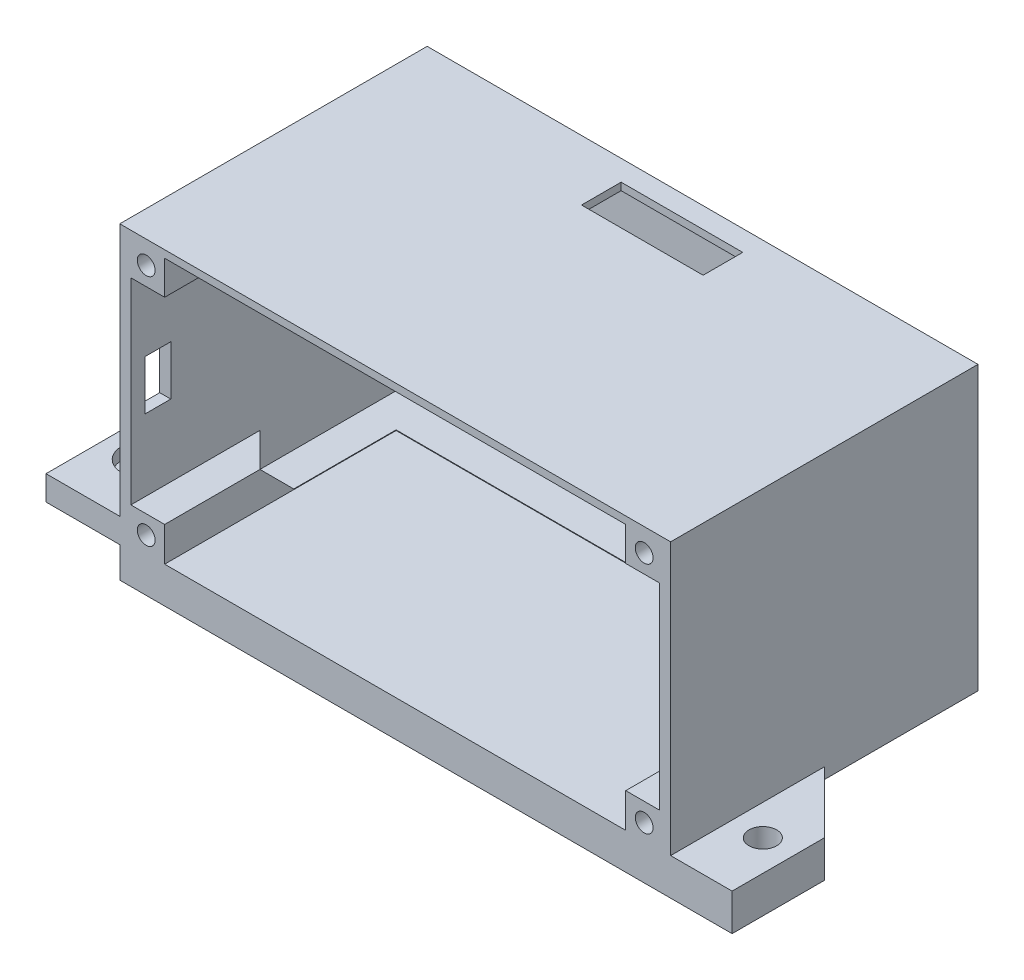
SolidWorks part; units mm, degrees
note: The reader was unsure of these and kept them because the rebuilt part matched: shared geometry of "Skizze1<3>".
ref_plane "Ebene vorne" through (0, 0, 0) normal (0, 0, 1) x (1, 0, 0)
ref_plane "Ebene oben" through (0, 0, 0) normal (0, 1, 0) x (1, 0, 0)
ref_plane "Ebene rechts" through (0, 0, 0) normal (1, 0, 0) x (0, 0, -1)
sketch "Skizze1" plane through (0, 0, 0) normal (0, 0, 1) x (1, 0, 0)
  line L0 (-44.8, 22.7) -> (-44.8, -23.3)
  line L1 (-43, -21.5) -> (43, -21.5)
  line L2 (-43, -21.5) -> (-43, 21.5)
  line L3 (-43, 21.5) -> (43, 21.5)
  line L4 (43, -21.5) -> (43, 21.5)
  line L5 (-43, -21.5) -> (43, 21.5) construction
  line L6 (-43, 21.5) -> (43, -21.5) construction
  line L7 (-44.8, -23.3) -> (44.8, -23.3)
  line L8 (44.8, -23.3) -> (44.8, 22.7)
  line L9 (44.8, 22.7) -> (-44.8, 22.7)
  point P0 (0, 0)
  dimension "D1" = 43
  dimension "D2" = 86
  dimension "D3" = 1.2
  dimension "D4" = 1.8
  dimension "D5" = 1.8
  dimension "D6" = 1.8
extrude "Aufsatz-Linear austragen1" add sketch "Skizze1" along normal blind 1 contours L1 L4 L3 L2 | L8 L9 L0 L7 L4 L1 L2 L3
extrude "Aufsatz-Linear austragen2" add sketch "Skizze1<3>" along normal blind 50
sketch "Skizze1<3>" plane through (0, 0, 0) normal (0, 0, 1) x (1, 0, 0) same geometry as "Skizze1"
sketch "Skizze2" plane through (0, 0, 50) normal (0, 0, 1) x (1, 0, 0)
  line L0 (43, 21.5) -> (-43, 21.5) construction
  line L1 (-43, -21.5) -> (-43, 21.5) construction
  line L2 (-43, 16) -> (-37.5, 16)
  line L3 (-43, 21.5) -> (-43, -21.5) construction
  line L4 (-37.5, 16) -> (-37.5, 21.5)
  line L5 (-37.5, 21.5) -> (-43, 21.5)
  line L6 (-43, 21.5) -> (-43, 16)
  line L7 (0, 0) -> (0, 11.0164) construction
  line L8 (0, 0) -> (-8.7102, 0) construction
  line L9 (-43, -21.5) -> (-43, -16)
  line L10 (-37.5, -21.5) -> (-43, -21.5)
  line L11 (-37.5, -16) -> (-37.5, -21.5)
  line L12 (-43, -16) -> (-37.5, -16)
  line L13 (43, -16) -> (37.5, -16)
  line L14 (37.5, -16) -> (37.5, -21.5)
  line L15 (37.5, -21.5) -> (43, -21.5)
  line L16 (43, -21.5) -> (43, -16)
  line L17 (43, 21.5) -> (43, 16)
  line L18 (37.5, 21.5) -> (43, 21.5)
  line L19 (37.5, 16) -> (37.5, 21.5)
  line L20 (43, 16) -> (37.5, 16)
  circle A0 centre (-40.5, 19) radius 1.45
  circle A1 centre (-40.5, -19) radius 1.45
  circle A2 centre (40.5, -19) radius 1.45
  circle A3 centre (40.5, 19) radius 1.45
  dimension "D1" = 2.9
  dimension "D2" = 2.5
  dimension "D3" = 2.5
  dimension "D4" = 3
extrude "Aufsatz-Linear austragen3" add sketch "Skizze2" against normal blind 15
sketch "Skizze3" plane through (0, 0, 35) normal (0, 0, -1) x (-1, 0, 0)
  line L0 (-43, 21.5) -> (-37.5, 21.5)
  line L1 (-37.5, 21.5) -> (-37.5, 16)
  line L2 (-37.5, 16) -> (-43, 16)
  line L3 (-43, 16) -> (-43, 21.5)
  line L4 (0, 0) -> (0, 9.0361)
  line L5 (0, 0) -> (8.9824, 0)
  line L6 (-43, -16) -> (-43, -21.5)
  line L7 (-37.5, -16) -> (-43, -16)
  line L8 (-37.5, -21.5) -> (-37.5, -16)
  line L9 (-43, -21.5) -> (-37.5, -21.5)
  line L10 (43, -21.5) -> (37.5, -21.5)
  line L11 (37.5, -21.5) -> (37.5, -16)
  line L12 (37.5, -16) -> (43, -16)
  line L13 (43, -16) -> (43, -21.5)
  line L14 (43, 16) -> (43, 21.5)
  line L15 (37.5, 16) -> (43, 16)
  line L16 (37.5, 21.5) -> (37.5, 16)
  line L17 (43, 21.5) -> (37.5, 21.5)
extrude "Aufsatz-Linear austragen4" add sketch "Skizze3" along normal blind 0.5 contours L3 L2 L1 L0 | L14 L17 L16 L15 | L13 L12 L11 L10
chamfer "Fase1" distance 5.5 angle 45 8 edges at (43, 18.75, 34.5) (40.25, 21.5, 34.5) (-40.25, -21.5, 34.5) (-43, -18.75, 34.5) (-43, 18.75, 34.5) (-40.25, 21.5, 34.5) (40.25, -21.5, 34.5) (43, -18.75, 34.5)
sketch "Skizze4" plane through (-44.8, 0, 0) normal (-1, 0, 0) x (0, 0, 1)
  line L0 (50, -0.3) -> (18.0685, -0.3) construction
  line L1 (50, 22.7) -> (50, -23.3) construction
  line L3 (43.5042, -4.3384) -> (47.6631, -4.3384)
  line L4 (43.5042, -4.3384) -> (43.5042, 3.7384)
  line L5 (43.5042, 3.7384) -> (47.6631, 3.7384)
  line L6 (47.6631, -4.3384) -> (47.6631, 3.7384)
  line L7 (43.5042, -4.3384) -> (47.6631, 3.7384) construction
  line L8 (43.5042, 3.7384) -> (47.6631, -4.3384) construction
  point P4 (45.5836, -0.3)
extrude "Schnitt-Linear austragen1" cut sketch "Skizze4" against normal blind 10
sketch "Skizze5" plane through (0, -23.3, 0) normal (0, -1, 0) x (1, 0, 0)
  line L0 (0, 0) -> (0, 29.1283) construction
  line L2 (0.8387, 3.5656) -> (22.8864, 3.5656)
  line L3 (0.8387, 3.5656) -> (0.8387, 12.3532)
  line L4 (0.8387, 12.3532) -> (22.8864, 12.3532)
  line L5 (22.8864, 3.5656) -> (22.8864, 12.3532)
  line L6 (0.8387, 3.5656) -> (22.8864, 12.3532) construction
  line L7 (0.8387, 12.3532) -> (22.8864, 3.5656) construction
  point P3 (11.8626, 7.9594)
extrude "Schnitt-Linear austragen2" cut sketch "Skizze5" against normal blind 10
sketch "Skizze6" plane through (0, 22.7, 0) normal (0, 1, 0) x (1, 0, 0)
  line L0 (0, 0) -> (0, -43.0102) construction
  line L1 (44.8, 0) -> (-44.8, 0) construction
  line L3 (-9.8897, -9.8025) -> (9.8897, -9.8025)
  line L4 (-9.8897, -9.8025) -> (-9.8897, -3.3605)
  line L5 (-9.8897, -3.3605) -> (9.8897, -3.3605)
  line L6 (9.8897, -9.8025) -> (9.8897, -3.3605)
  line L7 (-9.8897, -9.8025) -> (9.8897, -3.3605) construction
  line L8 (-9.8897, -3.3605) -> (9.8897, -9.8025) construction
  point P4 (0, -6.5815)
extrude "Schnitt-Linear austragen3" cut sketch "Skizze6" against normal blind 10
sketch "Skizze7" plane through (0, -23.3, 0) normal (0, -1, 0) x (1, 0, 0)
  line L0 (-41.4189, 45) -> (41.4189, 45)
  line L1 (41.4189, 45) -> (41.4189, 50)
  line L2 (41.4189, 50) -> (-41.4189, 50)
  line L3 (-44.8, 50) -> (44.8, 50) construction
  line L4 (0, 50) -> (0, 54.9207) construction
  line L5 (-41.4189, 45) -> (-41.4189, 50)
  point P10 (0, 45)
  dimension "D1" = 5
  dimension "D2" = 0
extrude "Aufsatz-Linear austragen5" [suppressed] add sketch "Skizze7" along normal blind 30
fillet "Verrundung1" [suppressed] radius 6
sketch "Skizze8" [suppressed] plane through (0, 0, 45) normal (0, 0, -1) x (-1, 0, 0)
  line L0 (0, -53.3) -> (0, -14.2567) construction
  line L1 (41.4189, -53.3) -> (-41.4189, -53.3) construction
  line L2 (0, -47) -> (-28.0842, -47) construction
  line L3 (44.8, -23.3) -> (-44.8, -23.3) construction
  circle A0 centre (-26.9, -47) radius 1.75
  circle A1 centre (26.9, -47) radius 1.75
  dimension "D3" = 3.5
  dimension "D1" = 23.7
  dimension "D2" = 53.8
extrude "Schnitt-Linear austragen4" [suppressed] cut sketch "Skizze8" against normal blind 30
fillet "Verrundung2" [suppressed] radius 6
sketch "Skizze9" plane through (44.8, 0, 0) normal (1, 0, 0) x (0, 0, -1)
  line L0 (-50, -27.5) -> (-50, -21.5)
  line L1 (-50, -23.3) -> (-50, 22.7) construction
  line L2 (-50, -21.5) -> (-30, -21.5)
  line L3 (-30, -21.5) -> (-30, -27.5)
  line L5 (-30, -27.5) -> (-50, -27.5)
  dimension "D1" = 20
  dimension "D2" = 6
extrude "Aufsatz-Linear austragen6" add sketch "Skizze9" along normal blind 10
sketch "Skizze10" plane through (0, -21.5, 0) normal (0, 1, 0) x (1, 0, 0)
  line L0 (49.8, -30) -> (49.8, -50) construction
  line L1 (54.8, -30) -> (44.8, -30) construction
  line L2 (54.8, -50) -> (44.8, -50) construction
  line L3 (0, 0) -> (0, -26.6574) construction
  line L4 (44.8, 0) -> (-44.8, 0) construction
  circle A0 centre (49.8, -40) radius 2.25
  circle A1 centre (-49.8, -40) radius 2.25
  dimension "D1" = 4.5
extrude "Schnitt-Linear austragen5" cut sketch "Skizze10" against normal blind 10
sketch "Skizze11" plane through (0, 0, 50) normal (0, 0, 1) x (1, 0, 0)
  line L0 (-37.5, -21.5) -> (-37.5, -21.6)
  line L1 (-37.5, -21.6) -> (37.5, -21.6)
  line L2 (37.5, -21.6) -> (37.5, -21.5)
  line L3 (37.5, -21.5) -> (-37.5, -21.5)
  dimension "D1" = 0.1
extrude "Schnitt-Linear austragen6" cut sketch "Skizze11" against normal up to vertex (37.6468 mm away) up to point (22.8864, -21.5, 12.3532)
sketch "Skizze12" plane through (0, 0, 50) normal (0, 0, 1) x (1, 0, 0)
  line L0 (-44.8, -22.5) -> (-56.8, -22.5)
  line L1 (-44.8, 22.7) -> (-44.8, -23.3) construction
  line L2 (-56.8, -22.5) -> (-56.8, -18.5)
  line L3 (-56.8, -18.5) -> (-44.8, -18.5)
  line L4 (-44.8, -18.5) -> (-44.8, -22.5)
  line L5 (-46.9573, -22.5) -> (-54.6427, -22.5) construction
  dimension "D2" = 4
  dimension "D3" = 12
extrude "Aufsatz-Linear austragen7" add sketch "Skizze12" against normal blind 20 contours L3 L4 L0 L2
sketch "Skizze13" plane through (0, -18.5, 0) normal (0, 1, 0) x (1, 0, 0)
  line L0 (-56.8, -50) -> (-44.8, -50) construction
  line L1 (-50.8, -50) -> (-50.8, -30) construction
  line L2 (-56.8, -30) -> (-44.8, -30) construction
  circle A0 centre (-50.8, -40) radius 2.25
  dimension "D1" = 4.5
  dimension "D2" = 10
extrude "Schnitt-Linear austragen7" cut sketch "Skizze13" against normal up to next
sketch "Skizze14" plane through (0, -18.5, 0) normal (0, 1, 0) x (1, 0, 0)
  circle A0 centre (-50.8, -40) radius 3.7
  dimension "D1" = 7.4
extrude "Schnitt-Linear austragen8" cut sketch "Skizze14" against normal blind 2
sketch "Skizze15" plane through (0, 0, 50) normal (0, 0, 1) x (1, 0, 0)
  line L0 (44.8, -21.5) -> (44.8, -23.3) construction
  line L1 (-44.8, -23.3) -> (44.8, -23.3) construction
  line L2 (44.8, -23.3) -> (44.8, -27.5)
  line L3 (-53.9573, -27.5) -> (246.0427, -27.5) construction
  line L4 (44.8, -27.5) -> (-44.8, -27.5)
  line L5 (-44.8, -23.3) -> (-44.8, -27.5)
  line L6 (-44.8, -23.3) -> (44.8, -23.3)
extrude "Aufsatz-Linear austragen8" add sketch "Skizze15" against normal blind 20
chamfer "Fase2" distance 4.5 angle 45 1 edges at (0, -23.3, 30)
chamfer "Fase3" distance 5 angle 45 1 edges at (44.8, -24.5, 30)
chamfer "Fase4" distance 5 angle 45 1 edges at (54.8, -24.5, 30)
chamfer "Fase5" distance 6 angle 45 2 edges at (-56.8, -20.5, 30) (-44.8, -20.5, 30)
